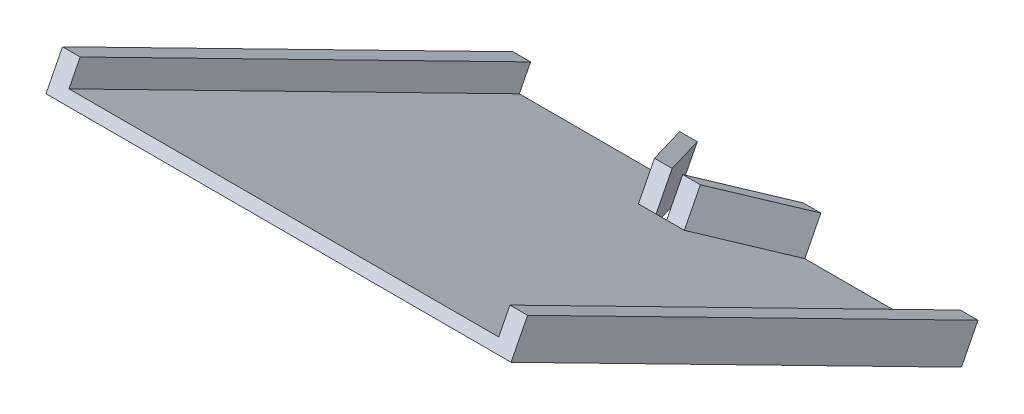
SolidWorks part; units mm, degrees
ref_plane "Front Plane" through (0, 0, 0) normal (0, 0, 1) x (1, 0, 0)
ref_plane "Top Plane" through (0, 0, 0) normal (0, 1, 0) x (1, 0, 0)
ref_plane "Right Plane" through (0, 0, 0) normal (1, 0, 0) x (0, 0, -1)
sketch "Sketch1" plane through (0, 0, 0) normal (1, 0, 0) x (0, 0, -1)
  line L0 (0, 0) -> (1275.5649, -649.9328)
  line L1 (0, 0) -> (15.0271, 29.4923)
  line L2 (15.0271, 29.4923) -> (1290.592, -620.4405)
  line L3 (1275.5649, -649.9328) -> (1290.592, -620.4405)
  dimension "D1" = 33.1
  dimension "D2" = 1431.6
extrude "Boss-Extrude1" add sketch "Sketch1" along normal blind 1317.1
sketch "Sketch6" plane through (0, 29.4923, -15.0271) normal (0, 0.891, -0.454) x (1, 0, 0)
  line L0 (1317.1, 1200) -> (673.5, 1200)
  line L1 (1317.1, 1431.6) -> (1317.1, 0) construction
  line L2 (0, 1431.6) -> (0, 0) construction
  line L3 (1317.1, 1431.6) -> (0, 1431.6) construction
  line L8 (643.5, 1200) -> (0, 1200)
  line L13 (508.5, 1431.6) -> (808.5, 1431.6)
  line L14 (643.5, 1200) -> (508.5, 1431.6)
  line L15 (673.5, 1200) -> (808.5, 1431.6)
  line L16 (643.5, 1200) -> (673.5, 1200)
  line L17 (643.5, 1200) -> (673.5, 1200)
  line M5 (1317.1, 1431.6) -> (0, 1431.6)
  dimension "D1" = 231.6
  dimension "D2" = 300
  dimension "D3" = 508.6
  dimension "D4" = 30
extrude "Cut-Extrude3" cut sketch "Sketch6" against normal through all contours L14 L16 L15 M5 region at (658.5, -582.2062, -1215.5531)
sketch "Sketch8" plane through (0, 29.4923, -15.0271) normal (0, 0.891, -0.454) x (1, 0, 0)
  line L0 (0, 1200) -> (1317.1, 1200)
  line L1 (0, 1431.6) -> (0, 0) construction
  line L2 (1317.1, 1431.6) -> (1317.1, 0) construction
  line L3 (808.5, 1431.6) -> (858.5, 1431.6)
  line L4 (1317.1, 1431.6) -> (808.5, 1431.6) construction
  line L5 (858.5, 1431.6) -> (723.5, 1200)
  line L6 (658.55, 1200) -> (658.55, 1121.7132) construction
  line L7 (673.5, 1200) -> (723.5, 1200)
  line L8 (673.5, 1200) -> (808.5, 1431.6)
  line L9 (643.6, 1200) -> (593.6, 1200)
  line L10 (458.6, 1431.6) -> (593.6, 1200)
  line L11 (508.6, 1431.6) -> (458.6, 1431.6)
  line L12 (643.6, 1200) -> (508.6, 1431.6)
  line L13 (0, 1431.6) -> (50, 1431.6)
  line L14 (1317.1, 0) -> (1267.1, 0)
  line L15 (1317.1, 0) -> (1317.1, 1431.6)
  line L16 (1317.1, 1431.6) -> (1267.1, 1431.6)
  line L17 (1267.1, 0) -> (1267.1, 1431.6)
  line L18 (50, 0) -> (50, 1431.6)
  line L19 (0, 0) -> (50, 0)
  line L20 (0, 0) -> (0, 1431.6)
  line M6 (643.5, 1200) -> (508.5, 1431.6)
  line M7 (508.5, 1431.6) -> (0, 1431.6)
  line M11 (1317.1, 1431.6) -> (808.5, 1431.6)
  line M12 (808.5, 1431.6) -> (673.5, 1200)
  dimension "D1" = 50
  dimension "D2" = 50
  dimension "D3" = 50
extrude "Boss-Extrude3" add sketch "Sketch8" along normal blind 70 contours L20 L13 L18 L19 | L17 L16 L15 L14
extrude "Boss-Extrude4" add sketch "Sketch8<4>" along normal blind 100 contours L5 L0 M11 M12 | L10 L0 M7 M6 region at (551.05, -567.8684, -1187.4135) region at (766, -567.8684, -1187.4135)
sketch "Sketch8<4>" plane through (0, 29.4923, -15.0271) normal (0, 0.891, -0.454) x (1, 0, 0) same geometry as "Sketch8"
